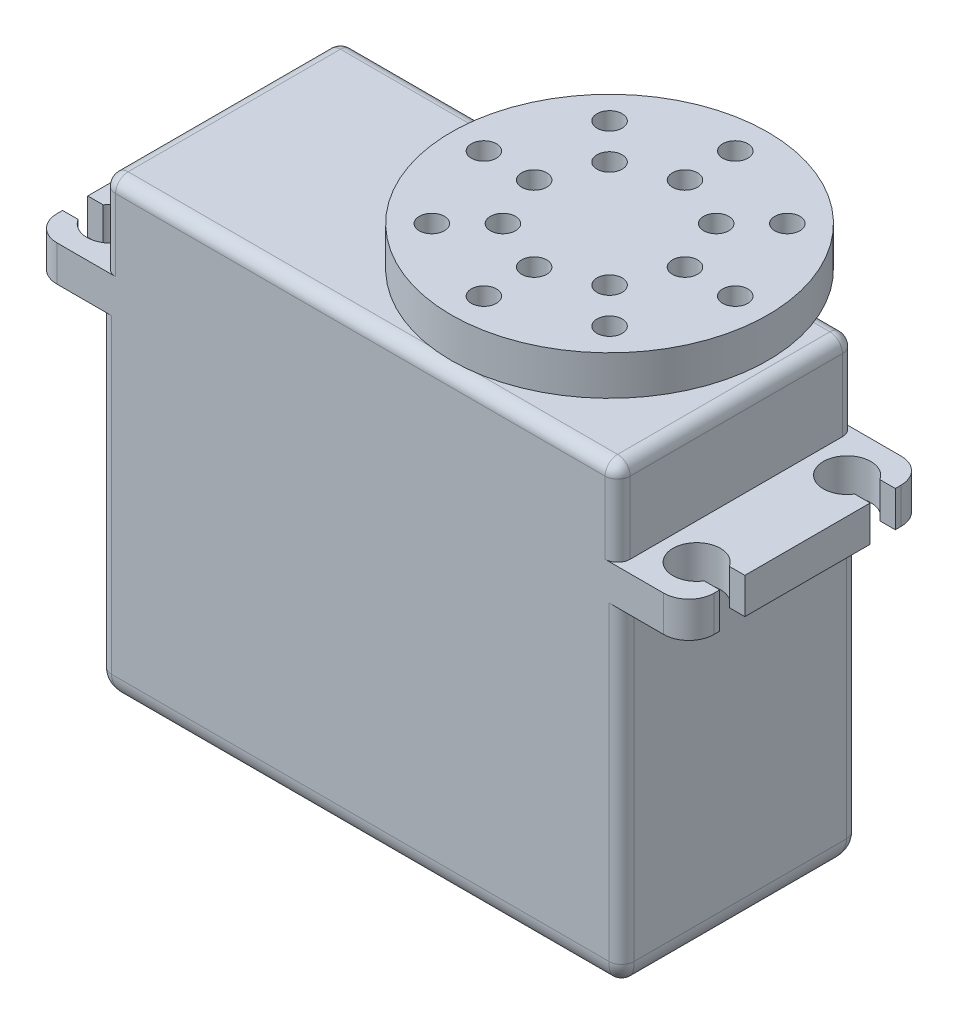
SolidWorks part; units mm, degrees
ref_plane "Front Plane" through (0, 0, 0) normal (0, 0, 1) x (1, 0, 0)
ref_plane "Top Plane" through (0, 0, 0) normal (0, 1, 0) x (1, 0, 0)
ref_plane "Right Plane" through (0, 0, 0) normal (1, 0, 0) x (0, 0, -1)
sketch "Sketch1" plane through (0, 0, 0) normal (0, 0, 1) x (1, 0, 0)
  line L1 (-33, 0) -> (33, 0)
  line L2 (-33, 0) -> (-33, -42.4)
  line L3 (-33.0018, 0) -> (33.0018, 0) construction
  line L4 (-33, -42.4) -> (33, -42.4)
  line L5 (33, 0) -> (33, -42.4)
  line L9 (-41.5, 15.2) -> (41.5, 15.2)
  line L10 (-41.5, 15.2) -> (-41.5, 0)
  line L11 (-41.5, 0) -> (41.5, 0)
  line L12 (41.5, 15.2) -> (41.5, 0)
  dimension "D1" = 83
  dimension "D2" = 15.2
  dimension "D3" = 42.4
  dimension "D4" = 66
sketch "Sketch2" plane through (0, 0, 0) normal (0, 0, 1) x (1, 0, 0)
  line L1 (-41.5, 15.2) -> (-32.5, 15.2)
  line L2 (-41.5, 15.2) -> (-41.5, 4.5203)
  line L3 (-41.5, 4.5203) -> (-32.5, 4.5203)
  line L4 (-32.5, 15.2) -> (-32.5, 4.5203)
  line L5 (41.5, 15.2) -> (32.5, 15.2)
  line L6 (41.5, 15.2) -> (41.5, 4.5203)
  line L7 (41.5, 4.5203) -> (32.5, 4.5203)
  line L8 (32.5, 15.2) -> (32.5, 4.5203)
  dimension "D1" = 9
  dimension "D2" = 9
extrude "Boss-Extrude1" add sketch "Sketch1" along normal blind 15 and the other way blind 14.986 contours L12 L9 L10 L11 L1 | L5 L1 L2 L4
extrude "Cut-Extrude1" cut sketch "Sketch2" against normal up to next and the other way up to next
ref_plane "Plane1" through (0, 4.5203, 0) normal (0, 1, 0) x (1, 0, 0)
ref_plane "Plane2" through (0, 15.2, 0) normal (0, 1, 0) x (1, 0, 0)
ref_plane "Plane6" through (0, 0, 0) normal (-1, 0, 0) x (0, 0, 1)
sketch "Sketch3" plane through (0, 4.5203, 0) normal (0, 1, 0) x (1, 0, 0)
  line L0 (37, 0) -> (37, 9.486) construction
  line L3 (0, 0) -> (37, 0) construction
  line L4 (37, 0) -> (37, -9.514) construction
  line L6 (41.5, 14.986) -> (32.5, 14.986) construction
  line L8 (32.5, -15) -> (32.5, 14.986) construction
  circle A0 centre (37, 9.486) radius 3
  circle A1 centre (37, -9.514) radius 3
  point P9 (37, 9.486)
  dimension "D1" = 19
  dimension "D2" = 6
  dimension "D3" = 6
  dimension "D4" = 5.5
  dimension "D5" = 4.5
extrude "Cut-Extrude2" cut sketch "Sketch3" against normal up to next
ref_plane "Plane3" through (41.5, 0, 0) normal (1, 0, 0) x (0, 0, -1)
ref_plane "Plane4" through (-41.5, 0, 0) normal (-1, 0, 0) x (0, 0, 1)
sketch "Sketch6" plane through (41.5, 0, 0) normal (1, 0, 0) x (0, 0, -1)
  line L0 (-0.007, 0) -> (9.486, 0) construction
  line L1 (14.986, 0) -> (-15, 0) construction
  line L2 (-0.007, 0) -> (-9.514, 0) construction
  line L3 (-6.514, 4.5203) -> (-12.514, 4.5203) construction
  line L4 (9.486, 0) -> (9.486, 4.5203) construction
  line L5 (-15, 4.5203) -> (14.986, 4.5203) construction
  line L6 (-9.514, 0) -> (-9.514, 4.5203) construction
  line L7 (12.486, 4.5203) -> (6.486, 4.5203) construction
  line L8 (7.8985, 0) -> (11.0735, 0)
  line L9 (7.8985, 0) -> (7.8985, 4.5203)
  line L10 (7.8985, 4.5203) -> (11.0735, 4.5203)
  line L11 (11.0735, 0) -> (11.0735, 4.5203)
  line L12 (7.8985, 0) -> (11.0735, 4.5203) construction
  line L13 (7.8985, 4.5203) -> (11.0735, 0) construction
  line L14 (-11.1015, 0) -> (-7.9265, 0)
  line L15 (-11.1015, 0) -> (-11.1015, 4.5203)
  line L16 (-11.1015, 4.5203) -> (-7.9265, 4.5203)
  line L17 (-7.9265, 0) -> (-7.9265, 4.5203)
  line L18 (-11.1015, 0) -> (-7.9265, 4.5203) construction
  line L19 (-11.1015, 4.5203) -> (-7.9265, 0) construction
  point P4 (9.486, 2.2602)
  point P10 (-9.514, 2.2602)
  point P11 (9.486, 2.2602)
  point P16 (-9.514, 2.2602)
  point P23 (0, 0)
  point P24 (0, 0)
  dimension "D1" = 7.8985
extrude "Cut-Extrude4" cut sketch "Sketch6" against normal up to next
mirror "Mirror1" about plane through (0, 0, 0) normal (-1, 0, 0) of "Cut-Extrude4", "Cut-Extrude2"
fillet "Fillet1" radius 3.175 8 edges at (33, -42.4, 0.007) (0, -42.4, 15) (0, -42.4, -14.986) (-33, -42.4, 0.007) (-41.5, 2.2602, 15) (-41.5, 2.2602, -14.986) (41.5, 2.2602, 15) (41.5, 2.2602, -14.986)
fillet "Fillet2" radius 1.5875 16 edges at (32.0701, -41.4701, -14.0561) (-32.0701, -41.4701, -14.0561) (-32.0701, -41.4701, 14.0701) (32.0701, -41.4701, 14.0701) (-32.5, 9.8602, 15) (-32.5, 9.8602, -14.986) (32.5, 9.8602, 15) (32.5, 9.8602, -14.986) (33, -19.6125, -14.986) (0, 15.2, -14.986) (0, 15.2, 15) (-32.5, 15.2, 0.007) (-33, -19.6125, -14.986) (-33, -19.6125, 15) (33, -19.6125, 15) (32.5, 15.2, 0.007)
sketch "Sketch10" plane through (0, 15.2, 0) normal (0, 1, 0) x (1, 0, 0)
  line L0 (0, 0) -> (16.4846, 0) construction
  circle A0 centre (16.4846, 0) radius 7.9375
extrude "Boss-Extrude2" add sketch "Sketch10" along normal blind 2.54 contours A0
fillet "Fillet3" radius 0.7937 1 edges at (16.4846, 17.74, 7.9375)
sketch "Sketch11" plane through (0, 15.2, 0) normal (0, 1, 0) x (1, 0, 0)
  circle A0 centre (16.4846, 0) radius 6.35
extrude "Boss-Extrude3" add sketch "Sketch11" along normal blind 6.35
ref_plane "Plane5" through (0, 21.55, 0) normal (0, 1, 0) x (1, 0, 0)
sketch "Sketch12" plane through (0, 21.55, 0) normal (0, 1, 0) x (1, 0, 0)
  circle A0 centre (16.4846, 0) radius 20
  dimension "D1" = 40
extrude "Boss-Extrude4" add sketch "Sketch12" along normal blind 4.9784 contours A0
sketch "Sketch14" plane through (0, 21.55, 0) normal (0, 1, 0) x (1, 0, 0)
  line L0 (16.4846, 0) -> (32.3596, 0) construction
  line L1 (16.4846, 0) -> (6.9596, 0) construction
  circle A0 centre (32.3596, 0) radius 1.5875
  circle A2 centre (6.9596, 0) radius 1.5875
sketch "Sketch15" plane through (0, 0, 0) normal (0, 0, 1) x (1, 0, 0)
  line L0 (16.4846, 21.55) -> (16.4846, 54.2) construction
extrude "Cut-Extrude6" cut sketch "Sketch14" along normal up to next
pattern_circular "CirPattern1" count 8 over 360 about axis through (16.4846, 0, 0) along (0, 1, 0) of "Cut-Extrude6"
